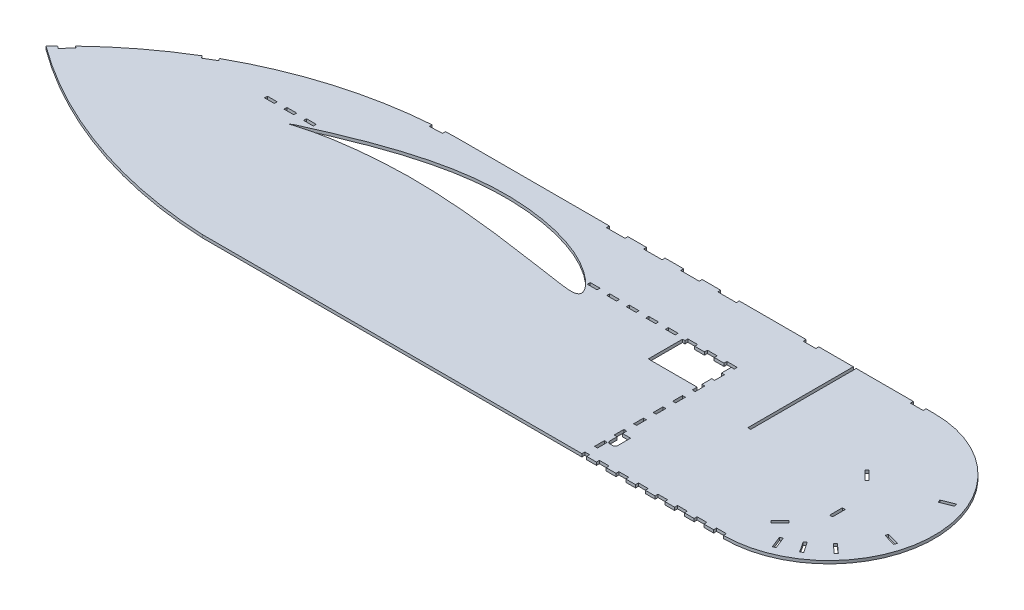
SolidWorks part; units mm, degrees
ref_plane "Front Plane" through (0, 0, 0) normal (0, 0, 1) x (1, 0, 0)
ref_plane "Top Plane" through (0, 0, 0) normal (0, 1, 0) x (1, 0, 0)
ref_plane "Right Plane" through (0, 0, 0) normal (1, 0, 0) x (0, 0, -1)
sketch "Sketch1" plane through (0, 0, 0) normal (0, 1, 0) x (1, 0, 0)
  line L0 (800, 108) -> (0, 108) construction
  line L1 (266.4083, 0) -> (800, 0)
  line L2 (0, 0) -> (0, 216) construction
  line L3 (316.2946, 216) -> (800, 216)
  arc A0 (800, 216) -> (800, 0) centre (800, 108) cw
  arc A2 (266.4083, 0) -> (19.4291, 86.8932) centre (286.1808, 450.645) cw
  arc A4 (19.4291, 86.8932) -> (316.2946, 216) centre (316.2946, -189.8565) cw
  dimension "D1" = 800
  dimension "D2" = 216
extrude "Boss-Extrude1" add sketch "Sketch1" along normal blind 3
sketch "Sketch2" plane through (0, 0, 0) normal (0, -1, 0) x (1, 0, 0)
  line L0 (605.07, -153) -> (605.07, 81) construction
  line L1 (647.57, -153) -> (637.57, -153)
  line L2 (655.07, -153) -> (655.07, -143)
  line L3 (655.07, -118) -> (605.07, -118)
  line L4 (823.6893, -121.2328) -> (814.4969, -130.4252)
  line L5 (814.4969, -130.4252) -> (816.6182, -132.5465)
  line L6 (816.6182, -132.5465) -> (825.8106, -123.3541)
  line L7 (825.8106, -123.3541) -> (823.6893, -121.2328)
  line L8 (823.6893, -121.2328) -> (814.4969, -130.4252)
  line L9 (814.4969, -130.4252) -> (816.6182, -132.5465)
  line L10 (816.6182, -132.5465) -> (825.8106, -123.3541)
  line L11 (825.8106, -123.3541) -> (823.6893, -121.2328)
  line L12 (605.07, -153) -> (605.07, -118)
  line L13 (778.5, -216) -> (791.5, -216) construction
  line L14 (791.5, -216) -> (791.5, -213) construction
  line L15 (791.5, -213) -> (778.5, -213) construction
  line L16 (778.5, -213) -> (778.5, -216) construction
  line L17 (668.6076, -216) -> (681.6076, -216) construction
  line L18 (681.6076, -216) -> (681.6076, -213) construction
  line L19 (681.6076, -213) -> (668.6076, -213) construction
  line L20 (833.1606, -28.1059) -> (837.9352, -16.0144)
  line L21 (837.9352, -16.0144) -> (835.1449, -14.9126)
  line L22 (835.1449, -14.9126) -> (830.3703, -27.0041)
  line L23 (830.3703, -27.0041) -> (833.1606, -28.1059)
  line L24 (833.1606, -28.1059) -> (837.9352, -16.0144)
  line L25 (837.9352, -16.0144) -> (835.1449, -14.9126)
  line L26 (835.1449, -14.9126) -> (830.3703, -27.0041)
  line L27 (830.3703, -27.0041) -> (833.1606, -28.1059)
  line L28 (839.4566, -85.3169) -> (839.4566, -72.3169)
  line L29 (839.4566, -72.3169) -> (836.4566, -72.3169)
  line L30 (836.4566, -72.3169) -> (836.4566, -85.3169)
  line L31 (836.4566, -85.3169) -> (839.4566, -85.3169)
  line L32 (839.4566, -85.3169) -> (839.4566, -72.3169)
  line L33 (839.4566, -72.3169) -> (836.4566, -72.3169)
  line L34 (836.4566, -72.3169) -> (836.4566, -85.3169)
  line L35 (836.4566, -85.3169) -> (839.4566, -85.3169)
  line L36 (668.6076, -213) -> (668.6076, -216) construction
  line L39 (600.2018, -213) -> (581.2018, -213) construction
  line L40 (658.07, -25.4734) -> (658.07, -38.6734)
  line L41 (663.77, -22.9734) -> (660.57, -22.9734)
  line L42 (666.27, -38.6734) -> (666.27, -25.4734)
  line L43 (658.07, -38.6734) -> (666.27, -38.6734)
  line L44 (658.07, -25.4734) -> (658.07, -33)
  line L45 (663.77, -22.9734) -> (660.57, -22.9734)
  line L46 (666.27, -38.6734) -> (666.27, -25.4734)
  line L47 (658.07, -38.6734) -> (666.27, -38.6734)
  line L48 (581.2018, -213) -> (581.2018, -216) construction
  line L49 (581.2018, -216) -> (600.2018, -216) construction
  line L50 (600.2018, -216) -> (600.2018, -213) construction
  line L51 (562.2018, -213) -> (543.2018, -213) construction
  line L52 (543.2018, -213) -> (543.2018, -216) construction
  line L53 (543.2018, -216) -> (562.2018, -216) construction
  line L54 (562.2018, -216) -> (562.2018, -213) construction
  line L55 (524.2018, -213) -> (505.2018, -213) construction
  line L56 (505.2018, -213) -> (505.2018, -216) construction
  line L57 (505.2018, -216) -> (524.2018, -216) construction
  line L58 (524.2018, -216) -> (524.2018, -213) construction
  line L59 (486.2018, -213) -> (467.2018, -213) construction
  line L60 (467.2018, -213) -> (467.2018, -216) construction
  line L61 (467.2018, -216) -> (486.2018, -216) construction
  line L62 (486.2018, -216) -> (486.2018, -213) construction
  line L63 (286.6536, -215.0679) -> (299.64, -215.6627) construction
  line L64 (299.64, -215.6627) -> (299.7772, -212.6658) construction
  line L65 (299.7772, -212.6658) -> (286.7909, -212.0711) construction
  line L66 (286.7909, -212.0711) -> (286.6536, -215.0679) construction
  line L67 (107.8918, -158.4076) -> (119.0512, -165.0761) construction
  line L68 (119.0512, -165.0761) -> (120.5901, -162.5008) construction
  line L69 (120.5901, -162.5008) -> (109.4307, -155.8323) construction
  line L70 (109.4307, -155.8323) -> (107.8918, -158.4076) construction
  line L71 (25.2251, -93.1105) -> (34.0897, -102.6194) construction
  line L72 (34.0897, -102.6194) -> (36.2841, -100.5738) construction
  line L73 (36.2841, -100.5738) -> (27.4195, -91.0649) construction
  line L74 (27.4195, -91.0649) -> (25.2251, -93.1105) construction
  line L75 (212.57, -142.2618) -> (212.57, -142.2948)
  line L131 (537.57, -153) -> (527.57, -153) construction
  line L132 (527.57, -153) -> (527.57, -156) construction
  line L133 (527.57, -156) -> (537.57, -156) construction
  line L134 (537.57, -156) -> (537.57, -153) construction
  line L135 (557.57, -153) -> (547.57, -153) construction
  line L136 (547.57, -153) -> (547.57, -156) construction
  line L137 (547.57, -156) -> (557.57, -156) construction
  line L138 (557.57, -156) -> (557.57, -153) construction
  line L139 (577.57, -153) -> (567.57, -153) construction
  line L140 (567.57, -153) -> (567.57, -156) construction
  line L141 (567.57, -156) -> (577.57, -156) construction
  line L142 (577.57, -156) -> (577.57, -153) construction
  line L143 (597.57, -153) -> (587.57, -153) construction
  line L144 (587.57, -153) -> (587.57, -156) construction
  line L145 (587.57, -156) -> (597.57, -156) construction
  line L146 (597.57, -156) -> (597.57, -153) construction
  line L148 (607.57, -153) -> (607.57, -156) construction
  line L149 (607.57, -156) -> (617.57, -156) construction
  line L150 (617.57, -156) -> (617.57, -153) construction
  line L152 (627.57, -153) -> (627.57, -156) construction
  line L153 (627.57, -156) -> (637.57, -156) construction
  line L154 (637.57, -156) -> (637.57, -153) construction
  line L155 (658.07, -153) -> (647.57, -153) construction
  line L156 (647.57, -153) -> (647.57, -156) construction
  line L157 (647.57, -156) -> (658.07, -156) construction
  line L158 (658.07, -156) -> (658.07, -153) construction
  line L160 (655.07, -143) -> (658.07, -143) construction
  line L161 (658.07, -143) -> (658.07, -133) construction
  line L162 (658.07, -133) -> (655.07, -133) construction
  line L163 (655.07, -113) -> (655.07, -123) construction
  line L164 (655.07, -123) -> (658.07, -123) construction
  line L165 (658.07, -123) -> (658.07, -113) construction
  line L166 (658.07, -113) -> (655.07, -113) construction
  line L167 (655.07, -93) -> (655.07, -103) construction
  line L168 (655.07, -103) -> (658.07, -103) construction
  line L169 (658.07, -103) -> (658.07, -93) construction
  line L170 (658.07, -93) -> (655.07, -93) construction
  line L171 (655.07, -73) -> (655.07, -83) construction
  line L172 (655.07, -83) -> (658.07, -83) construction
  line L173 (658.07, -83) -> (658.07, -73) construction
  line L174 (658.07, -73) -> (655.07, -73) construction
  line L175 (655.07, -53) -> (655.07, -63) construction
  line L176 (655.07, -63) -> (658.07, -63) construction
  line L177 (658.07, -63) -> (658.07, -53) construction
  line L178 (658.07, -53) -> (655.07, -53) construction
  line L179 (655.07, -33) -> (655.07, -43) construction
  line L180 (655.07, -43) -> (658.07, -43) construction
  line L182 (658.07, -33) -> (655.07, -33) construction
  line L183 (655.07, -13) -> (655.07, -23) construction
  line L184 (655.07, -23) -> (658.07, -23) construction
  line L185 (658.07, -23) -> (658.07, -13) construction
  line L186 (658.07, -13) -> (655.07, -13) construction
  line L187 (660, 0) -> (655.07, 0) construction
  line L188 (879.4887, -142.1211) -> (891.5217, -147.041) construction
  line L189 (891.5217, -147.041) -> (892.6571, -144.2642) construction
  line L190 (892.6571, -144.2642) -> (880.6241, -139.3442) construction
  line L191 (880.6241, -139.3442) -> (879.4887, -142.1211) construction
  line L192 (883.5475, -85.5833) -> (896.0431, -81.9972) construction
  line L193 (896.0431, -81.9972) -> (895.2156, -79.1136) construction
  line L194 (895.2156, -79.1136) -> (882.72, -82.6997) construction
  line L195 (882.72, -82.6997) -> (883.5475, -85.5833) construction
  line L196 (865.3607, -51.3372) -> (875.0343, -42.6526) construction
  line L197 (875.0343, -42.6526) -> (873.0302, -40.4202) construction
  line L198 (873.0302, -40.4202) -> (863.3566, -49.1048) construction
  line L199 (863.3566, -49.1048) -> (865.3607, -51.3372) construction
  line L200 (849.0648, -36.7585) -> (856.2517, -25.9258) construction
  line L201 (856.2517, -25.9258) -> (853.7518, -24.2673) construction
  line L202 (853.7518, -24.2673) -> (846.5649, -35.1) construction
  line L203 (846.5649, -35.1) -> (849.0648, -36.7585) construction
  line L204 (822.4089, -44.7346) -> (813.2165, -35.5422) construction
  line L205 (813.2165, -35.5422) -> (811.0952, -37.6635) construction
  line L206 (811.0952, -37.6635) -> (820.2876, -46.8559) construction
  line L207 (820.2876, -46.8559) -> (822.4089, -44.7346) construction
  line L208 (879.4887, -142.1211) -> (891.5217, -147.041)
  line L209 (891.5217, -147.041) -> (892.6571, -144.2642)
  line L210 (892.6571, -144.2642) -> (880.6241, -139.3442)
  line L211 (880.6241, -139.3442) -> (879.4887, -142.1211)
  line L212 (883.5475, -85.5833) -> (896.0431, -81.9972)
  line L213 (896.0431, -81.9972) -> (895.2156, -79.1136)
  line L214 (895.2156, -79.1136) -> (882.72, -82.6997)
  line L215 (882.72, -82.6997) -> (883.5475, -85.5833)
  line L216 (865.3607, -51.3372) -> (875.0343, -42.6526)
  line L217 (875.0343, -42.6526) -> (873.0302, -40.4202)
  line L218 (873.0302, -40.4202) -> (863.3566, -49.1048)
  line L219 (863.3566, -49.1048) -> (865.3607, -51.3372)
  line L220 (849.0648, -36.7585) -> (856.2517, -25.9258)
  line L221 (856.2517, -25.9258) -> (853.7518, -24.2673)
  line L222 (853.7518, -24.2673) -> (846.5649, -35.1)
  line L223 (846.5649, -35.1) -> (849.0648, -36.7585)
  line L224 (822.4089, -44.7346) -> (813.2165, -35.5422)
  line L225 (813.2165, -35.5422) -> (811.0952, -37.6635)
  line L226 (811.0952, -37.6635) -> (820.2876, -46.8559)
  line L227 (820.2876, -46.8559) -> (822.4089, -44.7346)
  line L228 (655.07, 0) -> (655.07, -3) construction
  line L229 (655.07, -3) -> (660, -3) construction
  line L230 (660, -3) -> (660, 0) construction
  line L231 (680, 0) -> (670, 0) construction
  line L232 (670, 0) -> (670, -3) construction
  line L233 (670, -3) -> (680, -3) construction
  line L234 (680, -3) -> (680, 0) construction
  line L235 (700, 0) -> (690, 0) construction
  line L236 (690, 0) -> (690, -3) construction
  line L237 (690, -3) -> (700, -3) construction
  line L238 (700, -3) -> (700, 0) construction
  line L239 (720, 0) -> (710, 0) construction
  line L240 (710, 0) -> (710, -3) construction
  line L241 (710, -3) -> (720, -3) construction
  line L242 (720, -3) -> (720, 0) construction
  line L243 (740, 0) -> (730, 0) construction
  line L244 (730, 0) -> (730, -3) construction
  line L245 (730, -3) -> (740, -3) construction
  line L246 (740, -3) -> (740, 0) construction
  line L247 (760, 0) -> (750, 0) construction
  line L248 (750, 0) -> (750, -3) construction
  line L249 (750, -3) -> (760, -3) construction
  line L250 (760, -3) -> (760, 0) construction
  line L251 (780, 0) -> (770, 0) construction
  line L252 (770, 0) -> (770, -3) construction
  line L253 (770, -3) -> (780, -3) construction
  line L254 (780, -3) -> (780, 0) construction
  line L255 (800, 0) -> (790, 0) construction
  line L256 (790, 0) -> (790, -3) construction
  line L257 (790, -3) -> (800, -3) construction
  line L258 (800, -3) -> (800, 0) construction
  line L259 (778.5, -216) -> (791.5, -216)
  line L260 (791.5, -216) -> (791.5, -213)
  line L261 (791.5, -213) -> (778.5, -213)
  line L262 (778.5, -213) -> (778.5, -216)
  line L263 (668.6076, -216) -> (681.6076, -216)
  line L264 (681.6076, -216) -> (681.6076, -213)
  line L265 (681.6076, -213) -> (668.6076, -213)
  line L266 (668.6076, -213) -> (668.6076, -216)
  line L267 (600.2018, -213) -> (581.2018, -213)
  line L268 (581.2018, -213) -> (581.2018, -216)
  line L269 (581.2018, -216) -> (600.2018, -216)
  line L270 (600.2018, -216) -> (600.2018, -213)
  line L271 (562.2018, -213) -> (543.2018, -213)
  line L272 (543.2018, -213) -> (543.2018, -216)
  line L273 (543.2018, -216) -> (562.2018, -216)
  line L274 (562.2018, -216) -> (562.2018, -213)
  line L275 (524.2018, -213) -> (505.2018, -213)
  line L276 (505.2018, -213) -> (505.2018, -216)
  line L277 (505.2018, -216) -> (524.2018, -216)
  line L278 (524.2018, -216) -> (524.2018, -213)
  line L279 (486.2018, -213) -> (467.2018, -213)
  line L280 (467.2018, -213) -> (467.2018, -216)
  line L281 (467.2018, -216) -> (486.2018, -216)
  line L282 (486.2018, -216) -> (486.2018, -213)
  line L283 (286.6536, -215.0679) -> (299.64, -215.6627)
  line L284 (299.64, -215.6627) -> (299.7772, -212.6658)
  line L285 (299.7772, -212.6658) -> (286.7909, -212.0711)
  line L286 (286.7909, -212.0711) -> (286.6536, -215.0679)
  line L287 (107.8918, -158.4076) -> (119.0512, -165.0761)
  line L288 (119.0512, -165.0761) -> (120.5901, -162.5008)
  line L289 (120.5901, -162.5008) -> (109.4307, -155.8323)
  line L290 (109.4307, -155.8323) -> (107.8918, -158.4076)
  line L291 (25.2251, -93.1105) -> (34.0897, -102.6194)
  line L292 (34.0897, -102.6194) -> (36.2841, -100.5738)
  line L293 (36.2841, -100.5738) -> (27.4195, -91.0649)
  line L294 (27.4195, -91.0649) -> (25.2251, -93.1105)
  line L351 (537.57, -153) -> (527.57, -153)
  line L352 (527.57, -153) -> (527.57, -156)
  line L353 (527.57, -156) -> (537.57, -156)
  line L354 (537.57, -156) -> (537.57, -153)
  line L355 (557.57, -153) -> (547.57, -153)
  line L356 (547.57, -153) -> (547.57, -156)
  line L357 (547.57, -156) -> (557.57, -156)
  line L358 (557.57, -156) -> (557.57, -153)
  line L359 (577.57, -153) -> (567.57, -153)
  line L360 (567.57, -153) -> (567.57, -156)
  line L361 (567.57, -156) -> (577.57, -156)
  line L362 (577.57, -156) -> (577.57, -153)
  line L363 (597.57, -153) -> (587.57, -153)
  line L364 (587.57, -153) -> (587.57, -156)
  line L365 (587.57, -156) -> (597.57, -156)
  line L366 (597.57, -156) -> (597.57, -153)
  line L368 (607.57, -153) -> (607.57, -156)
  line L369 (607.57, -156) -> (617.57, -156)
  line L370 (617.57, -156) -> (617.57, -153)
  line L372 (627.57, -153) -> (627.57, -156)
  line L373 (627.57, -156) -> (637.57, -156)
  line L374 (637.57, -156) -> (637.57, -153)
  line L375 (658.07, -153) -> (655.07, -153)
  line L376 (647.57, -153) -> (647.57, -156)
  line L377 (647.57, -156) -> (658.07, -156)
  line L378 (658.07, -156) -> (658.07, -153)
  line L380 (655.07, -143) -> (658.07, -143)
  line L381 (658.07, -143) -> (658.07, -133)
  line L382 (658.07, -133) -> (655.07, -133)
  line L383 (655.07, -113) -> (655.07, -118)
  line L384 (655.07, -123) -> (658.07, -123)
  line L385 (658.07, -123) -> (658.07, -113)
  line L386 (658.07, -113) -> (655.07, -113)
  line L387 (655.07, -93) -> (655.07, -103)
  line L388 (655.07, -103) -> (658.07, -103)
  line L389 (658.07, -103) -> (658.07, -93)
  line L390 (658.07, -93) -> (655.07, -93)
  line L391 (655.07, -73) -> (655.07, -83)
  line L392 (655.07, -83) -> (658.07, -83)
  line L393 (658.07, -83) -> (658.07, -73)
  line L394 (658.07, -73) -> (655.07, -73)
  line L395 (655.07, -53) -> (655.07, -63)
  line L396 (655.07, -63) -> (658.07, -63)
  line L397 (658.07, -63) -> (658.07, -53)
  line L398 (658.07, -53) -> (655.07, -53)
  line L399 (655.07, -33) -> (655.07, -43)
  line L400 (655.07, -43) -> (658.07, -43)
  line L401 (658.07, -43) -> (658.07, -38.6734)
  line L402 (658.07, -33) -> (655.07, -33)
  line L403 (655.07, -13) -> (655.07, -23)
  line L404 (655.07, -23) -> (658.07, -23)
  line L405 (658.07, -23) -> (658.07, -13)
  line L406 (658.07, -13) -> (655.07, -13)
  line L407 (660, 0) -> (655.07, 0)
  line L408 (655.07, 0) -> (655.07, -3)
  line L409 (655.07, -3) -> (660, -3)
  line L410 (660, -3) -> (660, 0)
  line L411 (680, 0) -> (670, 0)
  line L412 (670, 0) -> (670, -3)
  line L413 (670, -3) -> (680, -3)
  line L414 (680, -3) -> (680, 0)
  line L415 (700, 0) -> (690, 0)
  line L416 (690, 0) -> (690, -3)
  line L417 (690, -3) -> (700, -3)
  line L418 (700, -3) -> (700, 0)
  line L419 (720, 0) -> (710, 0)
  line L420 (710, 0) -> (710, -3)
  line L421 (710, -3) -> (720, -3)
  line L422 (720, -3) -> (720, 0)
  line L423 (740, 0) -> (730, 0)
  line L424 (730, 0) -> (730, -3)
  line L425 (730, -3) -> (740, -3)
  line L426 (740, -3) -> (740, 0)
  line L427 (760, 0) -> (750, 0)
  line L428 (750, 0) -> (750, -3)
  line L429 (750, -3) -> (760, -3)
  line L430 (760, -3) -> (760, 0)
  line L431 (780, 0) -> (770, 0)
  line L432 (770, 0) -> (770, -3)
  line L433 (770, -3) -> (780, -3)
  line L434 (780, -3) -> (780, 0)
  line L435 (800, 0) -> (790, 0)
  line L436 (790, 0) -> (790, -3)
  line L437 (790, -3) -> (800, -3)
  line L438 (800, -3) -> (800, 0)
  line L439 (655.07, -133) -> (655.07, -123)
  line L440 (627.57, -153) -> (617.57, -153)
  line L441 (607.57, -153) -> (605.07, -153)
  line L462 (187.07, -153) -> (177.07, -153) construction
  line L463 (177.07, -153) -> (177.07, -156) construction
  line L464 (177.07, -156) -> (187.07, -156) construction
  line L465 (187.07, -156) -> (187.07, -153) construction
  line L466 (207.07, -153) -> (197.07, -153) construction
  line L467 (197.07, -153) -> (197.07, -156) construction
  line L468 (197.07, -156) -> (207.07, -156) construction
  line L469 (207.07, -156) -> (207.07, -153) construction
  line L470 (227.07, -153) -> (217.07, -153) construction
  line L471 (217.07, -153) -> (217.07, -156) construction
  line L472 (217.07, -156) -> (227.07, -156) construction
  line L473 (227.07, -156) -> (227.07, -153) construction
  line L474 (517.57, -153) -> (507.57, -153) construction
  line L475 (507.57, -153) -> (507.57, -156) construction
  line L476 (507.57, -156) -> (517.57, -156) construction
  line L477 (517.57, -156) -> (517.57, -153) construction
  line L478 (187.07, -153) -> (177.07, -153)
  line L479 (177.07, -153) -> (177.07, -156)
  line L480 (177.07, -156) -> (187.07, -156)
  line L481 (187.07, -156) -> (187.07, -153)
  line L482 (207.07, -153) -> (197.07, -153)
  line L483 (197.07, -153) -> (197.07, -156)
  line L484 (197.07, -156) -> (207.07, -156)
  line L485 (207.07, -156) -> (207.07, -153)
  line L486 (227.07, -153) -> (217.07, -153)
  line L487 (217.07, -153) -> (217.07, -156)
  line L488 (217.07, -156) -> (227.07, -156)
  line L489 (227.07, -156) -> (227.07, -153)
  line L490 (517.57, -153) -> (507.57, -153)
  line L491 (507.57, -153) -> (507.57, -156)
  line L492 (507.57, -156) -> (517.57, -156)
  line L493 (517.57, -156) -> (517.57, -153)
  line L534 (717, -108) -> (717, -216)
  line L535 (717, -216) -> (720, -216)
  line L536 (720, -216) -> (720, -108)
  line L537 (720, -108) -> (717, -108)
  line L538 (717, -108) -> (717, -216)
  line L539 (717, -216) -> (720, -216)
  line L540 (720, -216) -> (720, -108)
  line L541 (720, -108) -> (717, -108)
  arc A2 (660.57, -22.9734) -> (658.07, -25.4734) centre (660.57, -25.4734) ccw
  arc A3 (666.27, -25.4734) -> (663.77, -22.9734) centre (663.77, -25.4734) ccw
  arc A4 (660.57, -22.9734) -> (658.07, -25.4734) centre (660.57, -25.4734) ccw
  arc A5 (666.27, -25.4734) -> (663.77, -22.9734) centre (663.77, -25.4734) ccw
  spline S0 degree 3 poles (-377.7086, -949.3382) (192.79, -108.7212) (198.5516, -134.0969) (215.6642, -144.2206) (218.7234, -145.7779) (222.7838, -147.5804) (227.7591, -149.7808) (233.6732, -152.3729) (243.3346, -156.474) (254.0716, -160.9286) (265.8113, -165.5514) (275.5598, -169.1926) (285.8203, -172.7897) (300.2132, -177.4429) (315.0475, -181.6144) (330.2168, -185.0782) (341.7168, -187.2628) (353.2384, -188.9705) (364.7498, -190.1898) (376.2222, -190.8893) (387.6115, -191.0869) (398.8538, -190.7647) (413.4214, -189.6963) (427.5808, -187.7) (441.1954, -184.8275) (450.8219, -182.3197) (459.9489, -179.4697) (468.5117, -176.2876) (476.4536, -172.8247) (483.7151, -169.1289) (490.2481, -165.2848) (496.0197, -161.4069) (500.998, -157.5857) (505.1476, -153.8841) (508.4473, -150.3827) (510.8522, -147.1808) (512.2305, -144.519) (512.6724, -142.438) (512.366, -140.694) (510.8363, -139.2679) (508.3008, -138.6046) (504.9907, -138.3969) (500.8451, -138.6329) (495.8864, -139.207) (490.1274, -140.0338) (483.6007, -141.0142) (476.346, -142.082) (468.4189, -143.2709) (459.8696, -144.553) (447.4042, -146.414) (434.3028, -148.292) (413.2306, -151.0803) (394.9165, -153.1705) (372.4131, -155.1852) (353.2786, -156.4974) (334.1039, -157.1205) (318.8375, -157.1193) (307.5693, -156.8631) (296.5448, -156.3424) (285.8536, -155.5986) (275.5863, -154.6546) (265.8296, -153.5569) (256.6735, -152.3128) (248.205, -150.9585) (240.5101, -149.5233) (233.6661, -148.0641) (227.7356, -146.6296) (222.7715, -145.2056) (218.7746, -143.9126) (215.7248, -142.9952) (197.5782, -138.4065) (176.9662, -150.5292) (372.0571, 844.703) knots -0.084186 -0.084186 -0.084186 -0.084186 0.001413 0.005226 0.010781 0.017816 0.026461 0.036791 0.048686 0.076639 0.092363 0.109003 0.126387 0.144339 0.181313 0.200023 0.218713 0.237261 0.255692 0.274037 0.292193 0.310133 0.327788 0.362002 0.378421 0.394287 0.409543 0.424114 0.437938 0.450942 0.463044 0.474154 0.484165 0.493024 0.500713 0.507126 0.51213 0.514904 0.517171 0.520262 0.524245 0.529498 0.536092 0.544061 0.553363 0.563905 0.575615 0.58842 0.602227 0.616944 0.648676 0.665501 0.718564 0.736789 0.773513 0.810245 0.828489 0.846493 0.864125 0.881249 0.897725 0.913415 0.928184 0.941897 0.954411 0.965603 0.97535 0.983576 0.990285 0.995433 0.9988 1.079713 1.079713 1.079713 1.079713 only from (212.57, -142.2948) to (212.57, -142.2618) construction
  spline S1 degree 3 poles (212.57, -142.2948) (212.8151, -142.4601) (213.7215, -143.0713) (215.6642, -144.2206) (218.7234, -145.7779) (222.7838, -147.5804) (227.7591, -149.7808) (233.6732, -152.3729) (243.3346, -156.474) (254.0716, -160.9286) (265.8113, -165.5514) (275.5598, -169.1926) (285.8203, -172.7897) (300.2132, -177.4429) (315.0475, -181.6144) (330.2168, -185.0782) (341.7168, -187.2628) (353.2384, -188.9705) (364.7498, -190.1898) (376.2222, -190.8893) (387.6115, -191.0869) (398.8538, -190.7647) (413.4214, -189.6963) (427.5808, -187.7) (441.1954, -184.8275) (450.8219, -182.3197) (459.9489, -179.4697) (468.5117, -176.2876) (476.4536, -172.8247) (483.7151, -169.1289) (490.2481, -165.2848) (496.0197, -161.4069) (500.998, -157.5857) (505.1476, -153.8841) (508.4473, -150.3827) (510.8522, -147.1808) (512.2305, -144.519) (512.6724, -142.438) (512.366, -140.694) (510.8363, -139.2679) (508.3008, -138.6046) (504.9907, -138.3969) (500.8451, -138.6329) (495.8864, -139.207) (490.1274, -140.0338) (483.6007, -141.0142) (476.346, -142.082) (468.4189, -143.2709) (459.8696, -144.553) (447.4042, -146.414) (434.3028, -148.292) (413.2306, -151.0803) (394.9165, -153.1705) (372.4131, -155.1852) (353.2786, -156.4974) (334.1039, -157.1205) (318.8375, -157.1193) (307.5693, -156.8631) (296.5448, -156.3424) (285.8536, -155.5986) (275.5863, -154.6546) (265.8296, -153.5569) (256.6735, -152.3128) (248.205, -150.9585) (240.5101, -149.5233) (233.6661, -148.0641) (227.7356, -146.6296) (222.7715, -145.2056) (218.7746, -143.9126) (215.7248, -142.9952) (213.7534, -142.4967) (212.8162, -142.3107) (212.57, -142.2618) knots 0 0 0 0 0.001413 0.005226 0.010781 0.017816 0.026461 0.036791 0.048686 0.076639 0.092363 0.109003 0.126387 0.144339 0.181313 0.200023 0.218713 0.237261 0.255692 0.274037 0.292193 0.310133 0.327788 0.362002 0.378421 0.394287 0.409543 0.424114 0.437938 0.450942 0.463044 0.474154 0.484165 0.493024 0.500713 0.507126 0.51213 0.514904 0.517171 0.520262 0.524245 0.529498 0.536092 0.544061 0.553363 0.563905 0.575615 0.58842 0.602227 0.616944 0.648676 0.665501 0.718564 0.736789 0.773513 0.810245 0.828489 0.846493 0.864125 0.881249 0.897725 0.913415 0.928184 0.941897 0.954411 0.965603 0.97535 0.983576 0.990285 0.995433 0.9988 1 1 1 1
  dimension "D6" = 35
  dimension "D1" = 0
  dimension "D2" = 0
  dimension "D3" = 0
  dimension "D4" = 0
  dimension "D5" = 0
extrude "Cut-Extrude1" cut sketch "Sketch2" against normal through all
